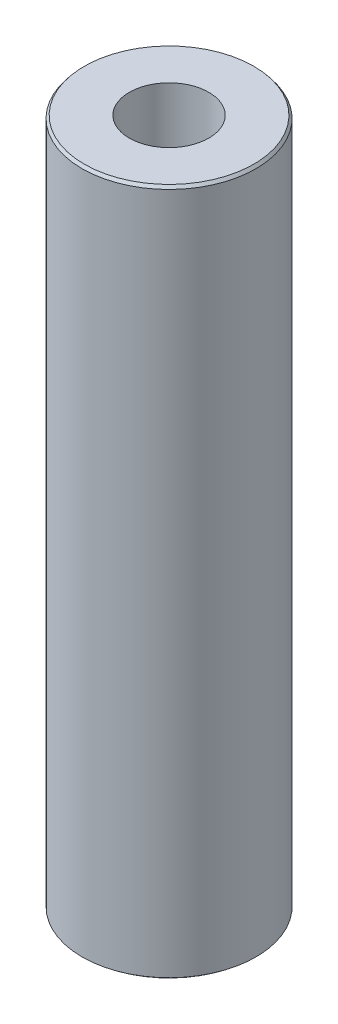
SolidWorks part; units mm, degrees
ref_plane "Front Plane" through (0, 0, 0) normal (0, 0, 1) x (1, 0, 0)
ref_plane "Top Plane" through (0, 0, 0) normal (0, 1, 0) x (1, 0, 0)
ref_plane "Right Plane" through (0, 0, 0) normal (1, 0, 0) x (0, 0, -1)
sketch "Sketch1" plane through (0, 0, 0) normal (0, 1, 0) x (1, 0, 0)
  circle A0 centre (0, 0) radius 50
  dimension "SHAFT_OD" = 100
extrude "Boss-Extrude1" add sketch "Sketch1" along normal blind 395.2232
sketch "Sketch2" plane through (0, 0, 0) normal (0, 1, 0) x (1, 0, 0)
  circle A0 centre (0, 0) radius 22.8403
  dimension "BORE_D" = 45.6806
extrude "Cut-Extrude1" cut sketch "Sketch2" along normal through all
chamfer "Chamfer1" distance 1.6098 angle 38.098 2 edges at (0, 395.2232, 50) (0, 0, 50) first distance on face at (0, 395.2232, 50) first distance on face at (0, 0, 22.8403)
